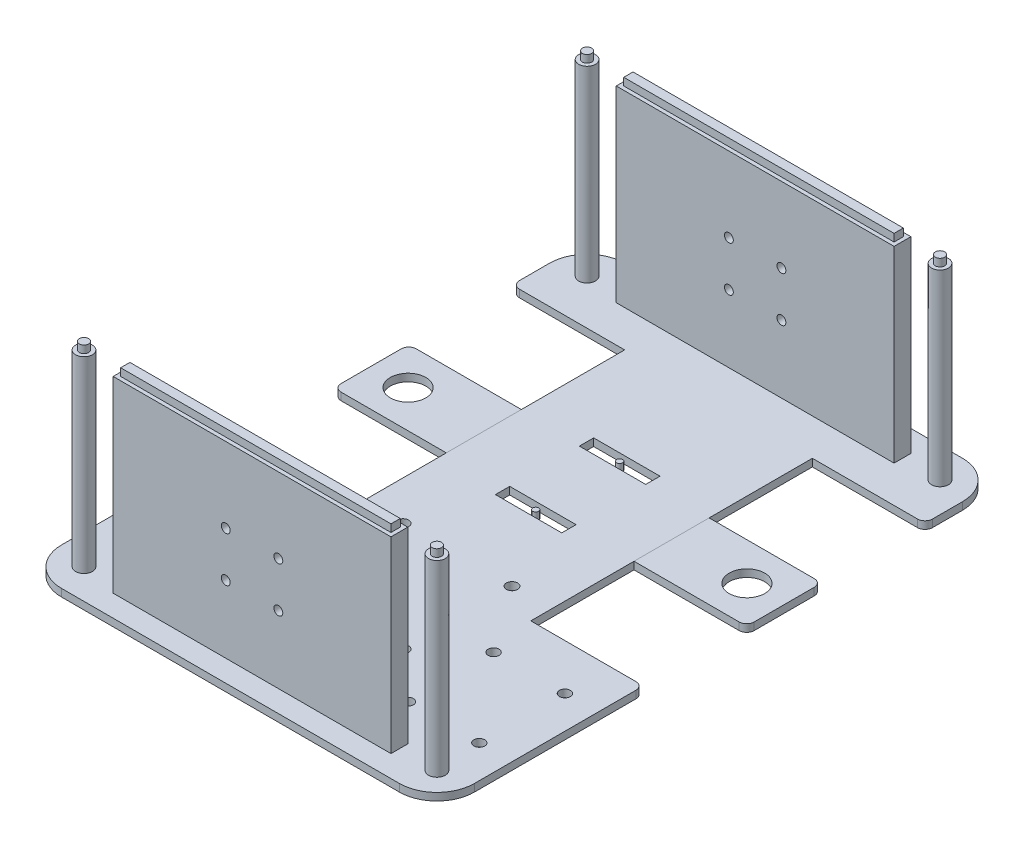
SolidWorks part; units mm, degrees
material "ABS"
ref_plane "Front Plane" through (0, 0, 0) normal (0, 0, 1) x (1, 0, 0)
ref_plane "Top Plane" through (0, 0, 0) normal (0, 1, 0) x (1, 0, 0)
ref_plane "Right Plane" through (0, 0, 0) normal (1, 0, 0) x (0, 0, -1)
sketch "Sketch2" plane through (0, 0, 0) normal (0, 1, 0) x (1, 0, 0)
  line L0 (-148.7583, 0) -> (98.0966, 0) construction
  line L1 (-69.85, -95.25) -> (69.85, -95.25)
  line L2 (-69.85, -95.25) -> (-69.85, 95.25)
  line L3 (-69.85, 95.25) -> (69.85, 95.25)
  line L4 (69.85, -95.25) -> (69.85, 95.25)
  line L5 (-69.85, -95.25) -> (69.85, 95.25) construction
  line L6 (-69.85, 95.25) -> (69.85, -95.25) construction
  line L7 (0, 121.1686) -> (0, -125.6862) construction
  point P0 (0, 0)
  dimension "D1" = 190.5
  dimension "D2" = 139.7
extrude "Base Plate" add sketch "Sketch2" along normal blind 2.54
sketch "Sketch4" plane through (0, 2.54, 0) normal (0, 1, 0) x (1, 0, 0)
  line L0 (0, -95.25) -> (0, 95.25) construction
  line L1 (-69.85, -95.25) -> (69.85, -95.25) construction
  line L2 (69.85, 95.25) -> (-69.85, 95.25) construction
  line L3 (-34.66, -69.85) -> (-34.66, -40.894) construction
  line L4 (-34.66, -40.894) -> (-58.79, -40.894) construction
  line L5 (-58.79, -40.894) -> (-58.79, -69.85) construction
  line L6 (-58.79, -69.85) -> (-34.66, -69.85) construction
  line L7 (69.85, -95.25) -> (69.85, 95.25) construction
  line L8 (-69.85, 95.25) -> (-69.85, -95.25) construction
  circle A0 centre (-58.79, -69.85) radius 1.8415
  circle A1 centre (-34.66, -69.85) radius 1.8415
  circle A2 centre (-34.66, -40.894) radius 1.8415
  circle A3 centre (-58.79, -40.894) radius 1.8415
  circle A4 centre (34.66, -69.85) radius 1.8415
  circle A5 centre (58.79, -69.85) radius 1.8415
  circle A6 centre (58.79, -40.894) radius 1.8415
  circle A7 centre (34.66, -40.894) radius 1.8415
  point P0 (-58.79, -69.85)
  point P1 (-58.79, -40.894)
  point P2 (-34.66, -40.894)
  point P3 (-34.66, -69.85)
  dimension "D4" = 3.683
  dimension "D1" = 28.956
  dimension "D2" = 24.13
  dimension "D3" = 11.06
  dimension "D5" = 25.4
extrude "L-Bracket holes" cut sketch "Sketch4" against normal blind 6.35
sketch "Sketch5" plane through (0, 2.54, 0) normal (0, 1, 0) x (1, 0, 0)
  line L0 (-69.85, -25.4) -> (-31.75, -25.4)
  line L1 (-69.85, 95.25) -> (-69.85, -95.25) construction
  line L2 (-31.75, -25.4) -> (-31.75, 69.85)
  line L3 (-31.75, 69.85) -> (-69.85, 69.85)
  line L4 (-69.85, 69.85) -> (-69.85, -25.4)
  line L5 (-69.85, -95.25) -> (69.85, -95.25) construction
  line L6 (69.85, 95.25) -> (-69.85, 95.25) construction
  line L7 (0, -95.25) -> (0, 95.25) construction
  line L8 (-58.79, -40.894) -> (-34.66, -40.894) construction
  line L9 (31.75, 69.85) -> (69.85, 69.85)
  line L10 (31.75, -25.4) -> (31.75, 69.85)
  line L11 (69.85, -25.4) -> (31.75, -25.4)
  line L12 (69.85, 69.85) -> (69.85, -25.4)
  dimension "D1" = 25.4
  dimension "D2" = 95.25
  dimension "D3" = 38.1
extrude "Steering Wheels Holes" cut sketch "Sketch5" against normal blind 6.35
fillet "Fillet1" radius 12.7 4 edges at (69.85, 1.27, -95.25) (-69.85, 1.27, -95.25) (69.85, 1.27, 95.25) (-69.85, 1.27, 95.25)
fillet "Fillet2" radius 2.54 4 edges at (69.85, 1.27, -69.85) (69.85, 1.27, 25.4) (-69.85, 1.27, 25.4) (-69.85, 1.27, -69.85)
sketch "Sketch6" plane through (0, 2.54, 0) normal (0, 1, 0) x (1, 0, 0)
  line L0 (-69.85, -95.25) -> (-69.85, 95.25) construction
  line L1 (-69.85, -95.25) -> (69.85, -95.25) construction
  line L2 (0, -88.935) -> (0, 95.5267) construction
  line L3 (-69.85, -27.94) -> (69.85, -27.94) construction
  point P0 (-59.69, -85.09)
  point P12 (-59.69, 29.21)
  point P13 (59.69, -85.09)
  point P14 (59.69, 29.21)
  dimension "D1" = 10.16
  dimension "D2" = 10.16
sketch "Sketch13" plane through (0, 2.54, 0) normal (0, 1, 0) x (1, 0, 0)
  line L0 (-69.85, -55.245) -> (69.85, -55.245) construction
  line L2 (-69.85, -27.94) -> (-69.85, -82.55) construction
  line L3 (69.85, -82.55) -> (69.85, -27.94) construction
  line L5 (-34.66, -69.85) -> (-34.66, -40.894) construction
  line L6 (34.66, -69.85) -> (34.66, -40.894) construction
  line L7 (-18.415, -55.245) -> (18.415, -55.245) construction
  line L8 (18.415, -55.245) -> (18.415, -18.415) construction
  line L9 (18.415, -18.415) -> (-18.415, -18.415) construction
  line L10 (-18.415, -18.415) -> (-18.415, -55.245) construction
  circle A0 centre (-18.415, -18.415) radius 1.905
  circle A1 centre (-18.415, -55.245) radius 1.905
  circle A2 centre (18.415, -55.245) radius 1.905
  circle A3 centre (18.415, -18.415) radius 1.905
  dimension "D1" = 3.81
  dimension "D4" = 36.83
  dimension "D5" = 36.83
extrude "Holes for L298" cut sketch "Sketch13" against normal blind 6.35
sketch "Sketch14" plane through (0, 2.54, 0) normal (0, 1, 0) x (1, 0, 0)
  line L0 (11.2203, 34.01) -> (-11.2203, 34.01)
  line L1 (11.2203, 5.61) -> (-11.2203, 5.61)
  line L2 (11.2203, 5.61) -> (11.2203, 10.44)
  line L3 (11.2203, 10.44) -> (-11.2203, 10.44)
  line L4 (0, 95.25) -> (0, -56.8347) construction
  line L5 (57.15, 95.25) -> (-57.15, 95.25) construction
  line L6 (-11.2203, 5.61) -> (-11.2203, 10.44)
  line L7 (-31.75, 22.225) -> (31.75, 22.225) construction
  line L8 (-31.75, -25.4) -> (-31.75, 69.85) construction
  line L9 (31.75, 69.85) -> (31.75, -25.4) construction
  line L10 (11.2203, 5.61) -> (-11.2203, 10.44) construction
  line L11 (11.2203, 10.44) -> (-11.2203, 5.61) construction
  line L12 (-11.2203, 38.84) -> (-11.2203, 34.01)
  line L13 (11.2203, 38.84) -> (-11.2203, 38.84)
  line L14 (11.2203, 38.84) -> (11.2203, 34.01)
  circle A2 centre (0, 8.025) radius 0.9906
  circle A3 centre (0, 36.425) radius 0.9906
  dimension "D3" = 4.83
  dimension "D2" = 1.9812
  dimension "D1" = 14.2
extrude "Cut-Extrude4" cut sketch "Sketch14" against normal blind 6.35
sketch "Sketch15" plane through (0, 2.54, 0) normal (0, 1, 0) x (1, 0, 0)
  line L0 (-69.85, -95.25) -> (-69.85, 95.25) construction
  line L1 (-69.85, 95.25) -> (69.85, 95.25) construction
  line L2 (0, 95.25) -> (0, 49.0943) construction
  line L3 (0, 121.1686) -> (0, -125.6862) construction
  circle A0 centre (-59.69, 85.09) radius 1.57
  circle A1 centre (-59.69, 85.09) radius 2.84
  point P0 (-59.69, 85.09)
  point P5 (59.69, 85.09)
  dimension "D3" = 3.14
  dimension "D1" = 10.16
  dimension "D2" = 10.16
  dimension "D4" = 1.27
extrude "Boss-Extrude3" add sketch "Sketch15" along normal blind 63.5
extrude "Boss-Extrude4" add sketch "Sketch15<2>" along normal blind 66.04 contours A0 region at (-59.69, 2.54, -85.09)
sketch "Sketch15<2>" plane through (0, 2.54, 0) normal (0, 1, 0) x (1, 0, 0) same geometry as "Sketch15"
mirror "Mirror1" about plane through (0, 0, 0) normal (1, 0, 0) of "Boss-Extrude4"
mirror "Mirror2" about plane through (0, 0, 0) normal (1, 0, 0) of "Boss-Extrude3"
sketch "Sketch23" plane through (0, 2.54, 0) normal (0, 1, 0) x (1, 0, 0)
  line L0 (0, 95.25) -> (0, -95.25) construction
  line L1 (-69.85, -27.94) -> (-69.85, -82.55) construction
  line L2 (-57.15, -95.25) -> (57.15, -95.25) construction
  circle A0 centre (-59.69, -85.09) radius 1.57
  circle A1 centre (-59.69, -85.09) radius 2.84
  dimension "D1" = 3.14
  dimension "D3" = 10.16
  dimension "D4" = 10.16
  dimension "D2" = 1.27
extrude "Boss-Extrude5" add sketch "Sketch23" along normal blind 63.5
extrude "Boss-Extrude6" add sketch "Sketch23<2>" along normal blind 66.04 contours A0 region at (-59.69, 2.54, 85.09)
sketch "Sketch23<2>" plane through (0, 2.54, 0) normal (0, 1, 0) x (1, 0, 0) same geometry as "Sketch23"
mirror "Mirror3" about plane through (0, 0, 0) normal (1, 0, 0) of "Boss-Extrude6", "Boss-Extrude5"
sketch "Sketch24" plane through (0, 2.54, 0) normal (0, 1, 0) x (1, 0, 0)
  line L0 (-59.69, -87.93) -> (59.69, -87.93) construction
  line L1 (-59.69, -82.25) -> (59.69, -82.25) construction
  line L2 (-59.69, 82.25) -> (59.69, 82.25) construction
  line L3 (-46.99, -87.93) -> (46.99, -87.93)
  line L4 (-46.99, -87.93) -> (-46.99, -82.25)
  line L5 (-46.99, -82.25) -> (46.99, -82.25)
  line L6 (46.99, -87.93) -> (46.99, -82.25)
  line L7 (59.69, 87.93) -> (-59.69, 87.93) construction
  line L9 (-46.99, 82.25) -> (46.99, 82.25)
  line L10 (-46.99, 82.25) -> (-46.99, 87.93)
  line L11 (-46.99, 87.93) -> (46.99, 87.93)
  line L12 (46.99, 82.25) -> (46.99, 87.93)
  circle A0 centre (-59.69, -85.09) radius 2.84 construction
  circle A1 centre (59.69, -85.09) radius 2.84 construction
  circle A2 centre (-59.69, -85.09) radius 2.84 construction
  circle A3 centre (-59.69, 85.09) radius 2.84 construction
  circle A4 centre (-59.69, 85.09) radius 2.84 construction
  circle A5 centre (59.69, 85.09) radius 2.84 construction
  circle A6 centre (59.69, 85.09) radius 2.84 construction
  dimension "D1" = 12.7
  dimension "D2" = 12.7
  dimension "D3" = 12.7
  dimension "D4" = 12.7
extrude "Boss-Extrude7" add sketch "Sketch24" along normal blind 63.5
sketch "Sketch25" plane through (0, 66.04, 0) normal (0, 1, 0) x (1, 0, 0)
  line L8 (-45.72, -83.52) -> (-45.72, -86.66)
  line L9 (-45.72, -86.66) -> (45.72, -86.66)
  line L10 (45.72, -86.66) -> (45.72, -83.52)
  line L11 (45.72, -83.52) -> (-45.72, -83.52)
  line L12 (-45.72, -83.52) -> (-45.72, -86.66)
  line L13 (-45.72, -86.66) -> (45.72, -86.66)
  line L14 (45.72, -86.66) -> (45.72, -83.52)
  line L15 (45.72, -83.52) -> (-45.72, -83.52)
  line L20 (-45.72, 86.66) -> (-45.72, 83.52)
  line L21 (-45.72, 83.52) -> (45.72, 83.52)
  line L22 (45.72, 83.52) -> (45.72, 86.66)
  line L23 (45.72, 86.66) -> (-45.72, 86.66)
  line L24 (-45.72, 86.66) -> (-45.72, 83.52)
  line L25 (-45.72, 83.52) -> (45.72, 83.52)
  line L26 (45.72, 83.52) -> (45.72, 86.66)
  line L27 (45.72, 86.66) -> (-45.72, 86.66)
  dimension "D1" = 1.27
  dimension "D2" = 1.27
extrude "Boss-Extrude8" add sketch "Sketch25" along normal blind 2.54
sketch "Sketch26" plane through (0, 0, -87.93) normal (0, 0, -1) x (-1, 0, 0)
  line L0 (0, 66.04) -> (0, 83.3576) construction
  line L1 (-46.99, 66.04) -> (46.99, 66.04) construction
  line L2 (-8.89, 40.64) -> (-8.89, -18.1923) construction
  circle A0 centre (-8.89, 40.64) radius 1.5
  circle A1 centre (-8.89, 25.4) radius 1.5
  circle A2 centre (8.89, 25.4) radius 1.5
  circle A3 centre (8.89, 40.64) radius 1.5
  dimension "D1" = 3
  dimension "D3" = 3
  dimension "D2" = 8.89
  dimension "D4" = 15.24
  dimension "D5" = 25.4
extrude "Cut-Extrude5" cut sketch "Sketch26" against normal through all
sketch "Sketch27" plane through (0, 2.54, 0) normal (0, 1, 0) x (1, 0, 0)
  line L0 (-31.75, -25.4) -> (-31.75, 69.85) construction
  line L1 (-31.75, 9.525) -> (-69.85, 9.525)
  line L2 (-31.75, 9.525) -> (-31.75, 34.925)
  line L3 (-31.75, 34.925) -> (-69.85, 34.925)
  line L4 (-69.85, 9.525) -> (-69.85, 34.925)
  line L5 (-69.85, -27.94) -> (-69.85, -82.55) construction
  line L6 (31.75, 22.225) -> (-61.2417, 22.225) construction
  line L7 (31.75, 69.85) -> (31.75, -25.4) construction
  line L8 (0, -95.25) -> (0, 114.9927) construction
  line L9 (-57.15, -95.25) -> (57.15, -95.25) construction
  line L10 (31.75, 34.925) -> (69.85, 34.925)
  line L11 (69.85, 9.525) -> (69.85, 34.925)
  line L12 (31.75, 9.525) -> (69.85, 9.525)
  line L13 (31.75, 9.525) -> (31.75, 34.925)
  point P13 (-31.75, 22.225)
  dimension "D1" = 25.4
extrude "Boss-Extrude9" add sketch "Sketch27" against normal through all separate body
sketch "Sketch28" plane through (0, 2.54, 0) normal (0, 1, 0) x (1, 0, 0)
  line L0 (0, -95.25) -> (0, 140.3564) construction
  circle A0 centre (57.3106, 22.1602) radius 6
  circle A1 centre (-57.3106, 22.1602) radius 6
  dimension "D1" = 12
extrude "Cut-Extrude6" cut sketch "Sketch28" against normal through all
fillet "Fillet4" radius 2.54 2 edges at (69.85, 1.27, -34.925) (69.85, 1.27, -9.525)
fillet "Fillet5" radius 2.54 2 edges at (-69.85, 1.27, -34.925) (-69.85, 1.27, -9.525)
